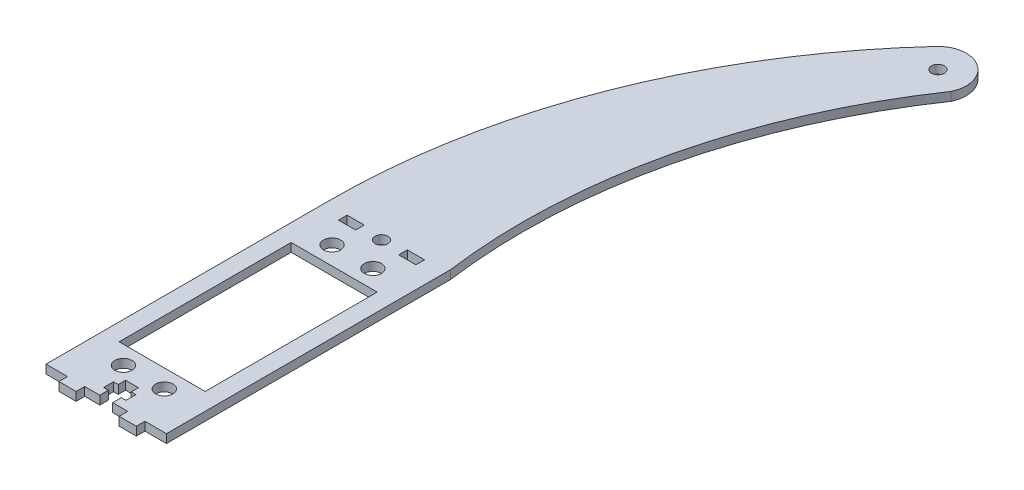
SolidWorks part; units mm, degrees
ref_plane "Front Plane" through (0, 0, 0) normal (0, 0, 1) x (1, 0, 0)
ref_plane "Top Plane" through (0, 0, 0) normal (0, 1, 0) x (1, 0, 0)
ref_plane "Right Plane" through (0, 0, 0) normal (1, 0, 0) x (0, 0, -1)
sketch "Sketch1" plane through (0, 0, 0) normal (0, 1, 0) x (1, 0, 0)
  line L0 (0, 33) -> (28, 33) construction
  line L1 (0, 0) -> (5, 0)
  line L2 (0, 0) -> (0, 66)
  line L3 (0, 66) -> (28, 66)
  line L4 (28, 0) -> (28, 66)
  line L5 (14, 66) -> (14, 0) construction
  line L6 (14, 57.25) -> (18.75, 57.25) construction
  line L7 (4, 13) -> (24, 13)
  line L8 (4, 13) -> (4, 53)
  line L9 (4, 53) -> (24, 53)
  line L10 (24, 13) -> (24, 53)
  line L11 (4, 13) -> (24, 53) construction
  line L12 (4, 53) -> (24, 13) construction
  line L13 (5, 0) -> (5, -2)
  line L19 (12.5, 6) -> (15.5, 6)
  line L20 (12.5, 6) -> (12.5, 4.3)
  line L33 (15.5, 6) -> (15.5, 4.3)
  line L34 (12.5, 6) -> (15.5, 0) construction
  line L35 (12.5, 0) -> (15.5, 6) construction
  line L36 (15.5, 2) -> (16.6, 2)
  line L38 (15.5, 4.3) -> (16.6, 4.3)
  line L39 (16.6, 2) -> (16.6, 4.3)
  line L41 (19, 0) -> (19, -2)
  line L42 (19, -2) -> (23, -2)
  line L43 (23, 0) -> (23, -2)
  line L44 (9, -2) -> (5, -2)
  line L45 (9, 0) -> (9, -2)
  line L46 (12.5, 2) -> (11.4, 2)
  line L47 (11.4, 2) -> (11.4, 4.3)
  line L48 (12.5, 4.3) -> (11.4, 4.3)
  line L49 (9, 0) -> (12.5, 0)
  line L50 (23, 0) -> (28, 0)
  line L51 (12.5, 2) -> (12.5, 0)
  line L52 (15.5, 2) -> (15.5, 0)
  line L53 (15.5, 0) -> (19, 0)
  line L54 (14, 64) -> (21, 64) construction
  line L55 (5, 65) -> (9, 65)
  line L56 (23, 63) -> (19, 63)
  line L57 (23, 63) -> (23, 65)
  line L58 (23, 65) -> (19, 65)
  line L59 (19, 63) -> (19, 65)
  line L60 (23, 63) -> (19, 65) construction
  line L61 (23, 65) -> (19, 63) construction
  line L62 (9, 63) -> (9, 65)
  line L63 (5, 63) -> (9, 63)
  line L64 (5, 63) -> (5, 65)
  circle A0 centre (18.75, 57.25) radius 2
  circle A1 centre (9.25, 57.25) radius 2
  circle A2 centre (18.75, 8.75) radius 2
  circle A3 centre (9.25, 8.75) radius 2
  circle A6 centre (14, 64) radius 1.5
  point P9 (14, 33)
  point P23 (14, 3)
  point P36 (19, -1)
  dimension "D5" = 4
  dimension "D8" = 5
  dimension "D18" = 3
  dimension "D1" = 28
  dimension "D2" = 66
  dimension "D3" = 20
  dimension "D4" = 40
  dimension "D6" = 4.75
  dimension "D7" = 4.25
  dimension "D9" = 4
  dimension "D10" = 2
  dimension "D11" = 3
  dimension "D12" = 6
  dimension "D13" = 1.1
  dimension "D14" = 2.3
  dimension "D15" = 2
  dimension "D16" = 4
  dimension "D17" = 2
  dimension "D19" = 5
  dimension "D20" = 1
extrude "Boss-Extrude1" add sketch "Sketch1" along normal blind 2
sketch "Sketch2" plane through (0, 2, 0) normal (0, 1, 0) x (1, 0, 0)
  line L0 (0, 66) -> (150, 66) construction
  line L1 (150, 66) -> (28, 66) construction
  line L2 (0, 66) -> (161.7933, 84.01) construction
  line L3 (161.7933, 84.01) -> (28, 66) construction
  line L4 (64.776, 189.4377) -> (70.3785, 183.3496) construction
  line L5 (0, 66) -> (28, 66)
  arc A0 (64.776, 189.4377) -> (0, 66) centre (150, 66) ccw
  arc A1 (70.3785, 183.3496) -> (28, 66) centre (161.7933, 84.01) ccw
  arc A2 (64.776, 189.4377) -> (70.3785, 183.3496) centre (67.1495, 186) cw
  point P6 (64.776, 189.4377)
  point P8 (125.0223, 213.9058)
  dimension "D1" = 300
  dimension "D2" = 270
  dimension "D3" = 120
extrude "Boss-Extrude2" add sketch "Sketch2" against normal blind 2
sketch "Sketch4" plane through (0, 2, 0) normal (0, 1, 0) x (1, 0, 0)
  line L0 (39.4544, 167.3888) -> (49.2781, 158.6112) construction
  line L1 (24, 53) -> (4, 53) construction
  line L2 (49.2781, 158.6112) -> (90.3366, 196.3334)
  line L3 (90.3366, 196.3334) -> (75.55, 212.4278)
  line L4 (75.55, 212.4278) -> (35.4691, 175.6037)
  line L5 (35.4691, 175.6037) -> (39.4544, 167.3888)
  arc A0 (64.776, 189.4377) -> (0, 66) centre (150, 66) ccw construction
  arc A1 (70.3785, 183.3496) -> (28, 66) centre (161.7933, 84.01) ccw construction
  circle A2 centre (44.3663, 163) radius 1.5
  arc A3 (39.4544, 167.3888) -> (49.2781, 158.6112) centre (44.3663, 163) cw
  dimension "D1" = 3
  dimension "D2" = 110
extrude "Cut-Extrude1" cut sketch "Sketch4" against normal blind 2
